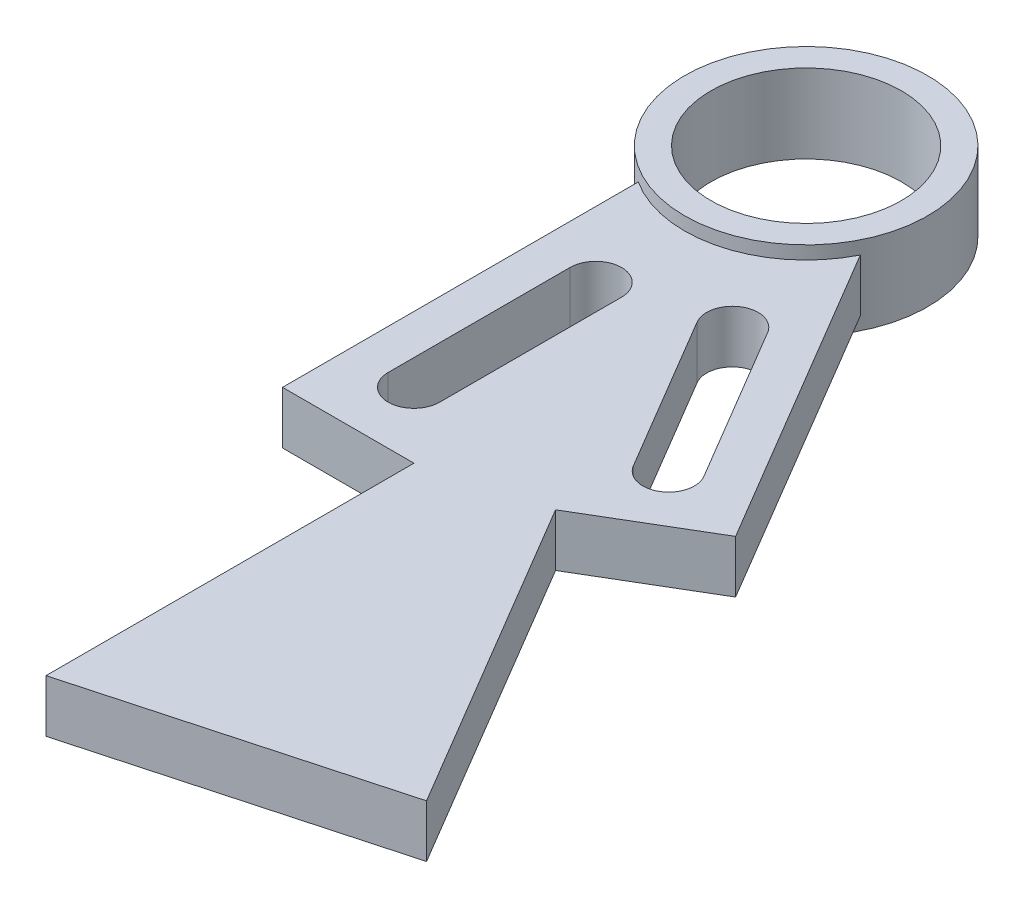
SolidWorks part; units mm, degrees
material "AISI 4130 Steel, annealed at 865C"
ref_plane "Front Plane" through (0, 0, 0) normal (0, 0, 1) x (1, 0, 0)
ref_plane "Top Plane" through (0, 0, 0) normal (0, 1, 0) x (1, 0, 0)
ref_plane "Right Plane" through (0, 0, 0) normal (1, 0, 0) x (0, 0, -1)
sketch "Sketch1" plane through (0, 0, 0) normal (0, 1, 0) x (1, 0, 0)
  line L0 (0, -50.4952) -> (0, -14.6812) construction
  line L1 (25.7366, -43.4441) -> (7.4828, -12.6311) construction
  line L2 (0, -47.3837) -> (0, -25.4127) construction
  line L5 (-3.1115, -47.3837) -> (-3.1115, -25.4127)
  line L8 (-7.9375, -55.3212) -> (7.9375, -55.3212)
  line L9 (21.3672, -51.6418) -> (35.0255, -43.5506)
  line L10 (-7.9375, -55.3212) -> (-7.9375, -12.3505)
  line L11 (35.0255, -43.5506) -> (13.124, -6.5802)
  line L12 (7.9375, -55.3212) -> (7.9375, -99.7712)
  line L13 (21.3672, -51.6418) -> (44.0227, -89.8849)
  line L14 (7.9375, -99.7712) -> (44.0227, -89.8849)
  line L15 (0, -14.6812) -> (0, 0) construction
  line L16 (0, -55.3212) -> (0, -50.4952) construction
  line L17 (28.1964, -47.5962) -> (25.7366, -43.4441)
  line L18 (3.1115, -47.3837) -> (3.1115, -25.4127)
  line L19 (12.9525, -21.8641) -> (24.1507, -40.7671) construction
  line L20 (15.6295, -20.2782) -> (26.8277, -39.1812)
  line L21 (10.2754, -23.45) -> (21.4737, -42.353)
  line L22 (7.4828, -12.6311) -> (0, 0) construction
  line L23 (0, 0) -> (20.1346, -73.4918) construction
  line L25 (178.0398, -300.5362) -> (14.7666, -24.9265) construction
  line L27 (0, 0) -> (25.9801, -94.8281) construction
  circle A0 centre (0, 0) radius 11.5062
  circle A1 centre (0, 0) radius 14.6812
  arc A2 (-3.1115, -47.3837) -> (3.1115, -47.3837) centre (0, -47.3837) ccw
  arc A3 (3.1115, -25.4127) -> (-3.1115, -25.4127) centre (0, -25.4127) ccw
  arc A4 (15.6295, -20.2782) -> (10.2754, -23.45) centre (12.9525, -21.8641) ccw
  arc A5 (21.4737, -42.353) -> (26.8277, -39.1812) centre (24.1507, -40.7671) ccw
  point P9 (0, -36.3982)
  point P14 (18.5516, -31.3156)
  point P23 (0, -55.3212)
  point P26 (28.1964, -47.5962)
  point P33 (0, -50.4952)
  point P36 (25.7366, -43.4441)
  point P38 (0, -22.3012)
  dimension "D2" = 29.3624
  dimension "D3" = 40.64
  dimension "D4" = 4.826
  dimension "D6" = 44.45
  dimension "D7" = 7.9375
  dimension "D5" = 4.826
  dimension "D8" = 7.62
  dimension "D9" = 76.2
extrude "Bearing extrude" add sketch "Sketch1" along normal mid plane 9.525 contours A1 A0 region at (-6.8368, 0, -12.521)
extrude "Boss-Extrude2" add sketch "Sketch1<5>" along normal mid plane 6.35 contours A1 L10 L8 L12 L14 L13 L9 L11 A4 A2 region at (15.3609, 0, 56.0678)
sketch "Sketch1<5>" plane through (0, 0, 0) normal (0, 1, 0) x (1, 0, 0) same geometry as "Sketch1"
sketch3d "Tab Point"
  line L0 (20.1346, 0, 73.4918) -> (20.1346, 23.7085, 73.4918) construction
  line L1 (0, 0, 0) -> (20.1346, 0, 73.4918) construction
  line L2 (0, 0, 0) -> (25.9801, 0, 94.8281) construction
equation "\"Apex_thickness\"= .25"
equation "\"Bearing_diameter\"= .906"
equation "\"A-arm_angle\"= 32.91"
equation "\"D1@Sketch1\"=\"Bearing_diameter\""
equation "\"D1@Boss-Extrude2\"= \"Apex_thickness\""
equation "\"apex slot\"= 1.4"
equation "\"tube diameter\"= 5 / 8"
